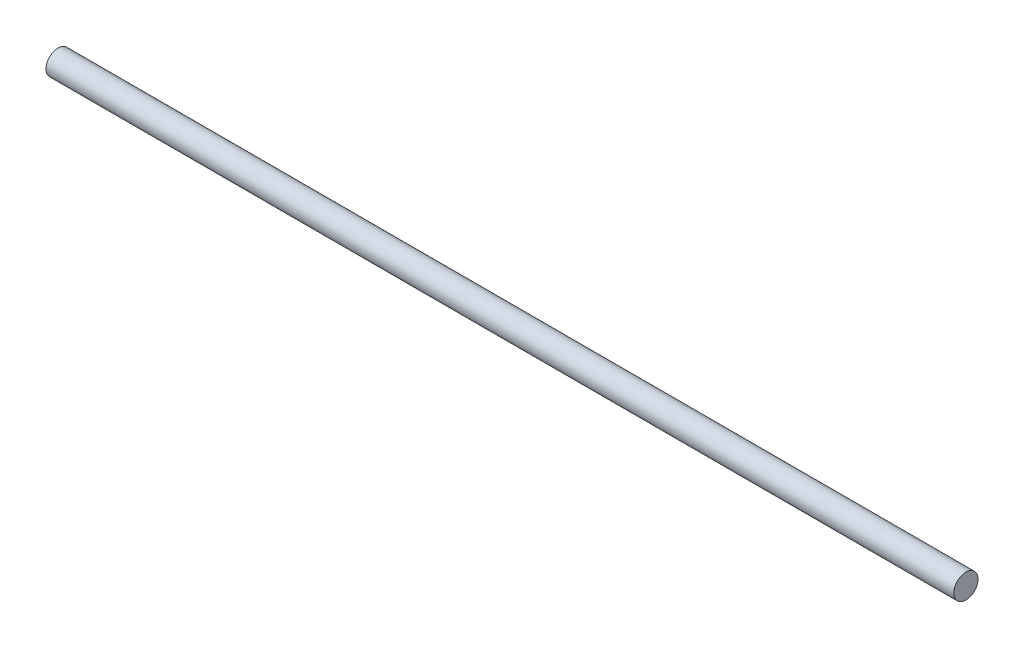
SolidWorks part; units mm, degrees
ref_plane "Front Plane" through (0, 0, 0) normal (0, 0, 1) x (1, 0, 0)
ref_plane "Top Plane" through (0, 0, 0) normal (0, 1, 0) x (1, 0, 0)
ref_plane "Right Plane" through (0, 0, 0) normal (1, 0, 0) x (0, 0, -1)
sketch "Sketch1" plane through (0, 0, 0) normal (1, 0, 0) x (0, 0, -1)
  circle A0 centre (0, 0) radius 4
  dimension "D1" = 8
extrude "Boss-Extrude1" add sketch "Sketch1" along normal blind 150 and the other way blind 150
ref_axis "Axis1" through (165, 0, 0) along (-1, 0, 0)
